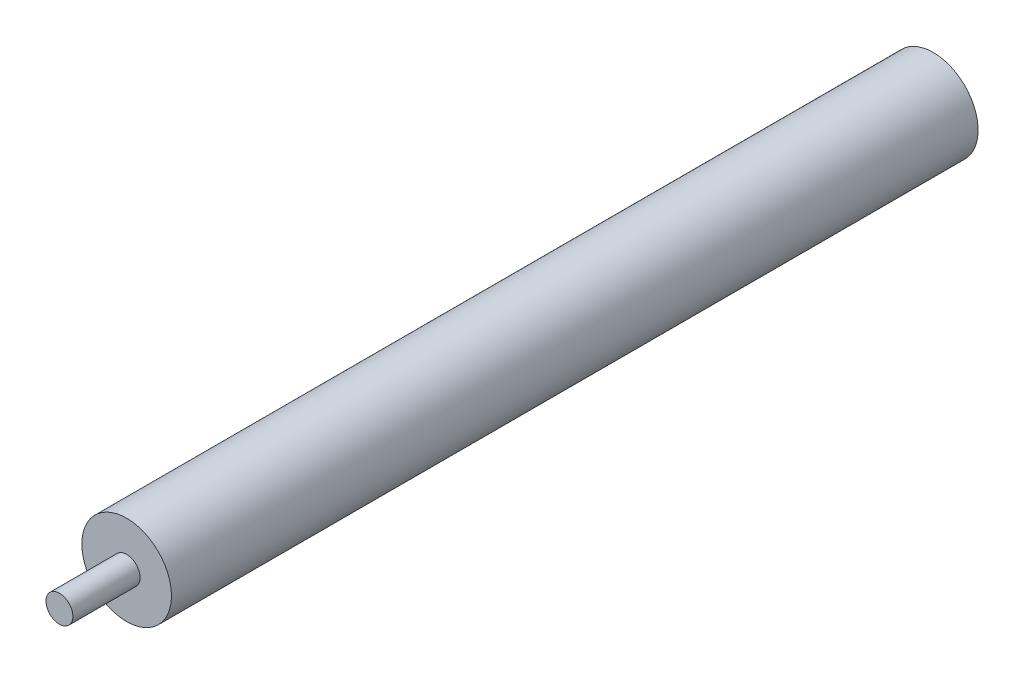
SolidWorks part; units mm, degrees
material "4032-T6"
ref_plane "Front Plane" through (0, 0, 0) normal (0, 0, 1) x (1, 0, 0)
ref_plane "Top Plane" through (0, 0, 0) normal (0, 1, 0) x (1, 0, 0)
ref_plane "Right Plane" through (0, 0, 0) normal (1, 0, 0) x (0, 0, -1)
sketch "Sketch1" plane through (0, 0, 0) normal (0, 0, 1) x (1, 0, 0)
  circle A0 centre (0, 0) radius 10
  dimension "D1" = 20
extrude "Boss-Extrude1" add sketch "Sketch1" along normal blind 180
sketch "Sketch2" plane through (0, 0, 180) normal (0, 0, 1) x (1, 0, 0)
  circle A0 centre (0, 0) radius 3
extrude "Boss-Extrude2" add sketch "Sketch2" along normal blind 15
